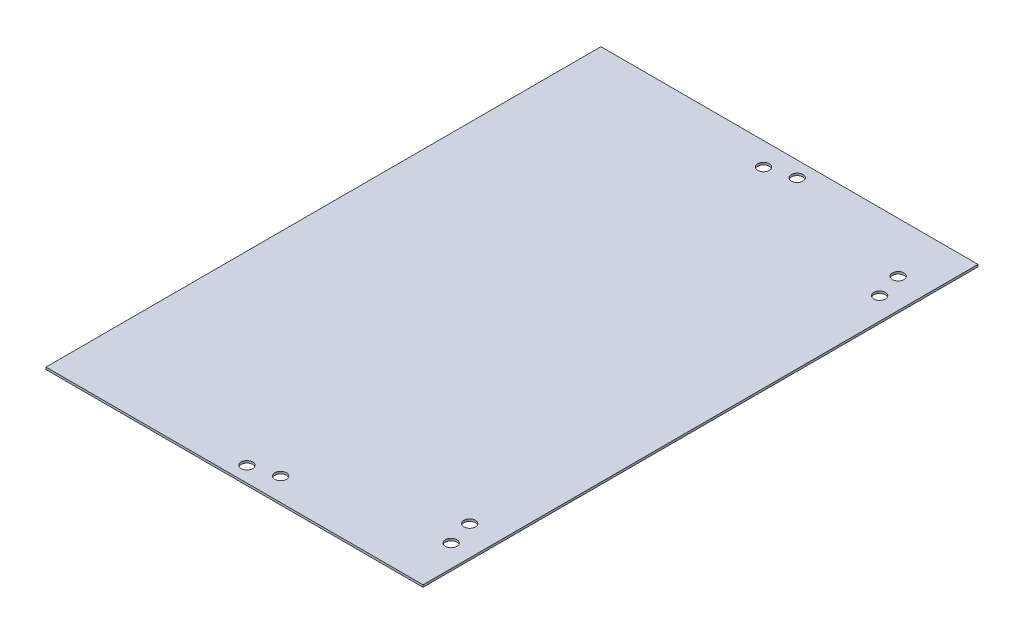
SolidWorks part; units mm, degrees
material "Alumina"
ref_plane "Front Plane" through (0, 0, 0) normal (0, 0, 1) x (1, 0, 0)
ref_plane "Top Plane" through (0, 0, 0) normal (0, 1, 0) x (1, 0, 0)
ref_plane "Right Plane" through (0, 0, 0) normal (1, 0, 0) x (0, 0, -1)
sketch "Sketch3" plane through (0, 0, 0) normal (0, 1, 0) x (1, 0, 0)
  line L1 (-110, 161.9) -> (110, 161.9)
  line L2 (-110, 161.9) -> (-110, -161.9)
  line L3 (-110, -161.9) -> (110, -161.9)
  line L4 (110, 161.9) -> (110, -161.9)
  line L5 (-110, 161.9) -> (110, -161.9) construction
  line L6 (-110, -161.9) -> (110, 161.9) construction
  point P0 (0, 0)
  dimension "D1" = 323.8
  dimension "D2" = 220
extrude "Boss-Extrude1" add sketch "Sketch3" along normal blind 1.2954
sketch "Sketch4" plane through (0, 1.2954, 0) normal (0, 1, 0) x (1, 0, 0)
  circle A0 centre (97.1046, -132.62) radius 3.3782
  circle A1 centre (92.7046, -117.38) radius 3.3782
  circle A2 centre (13.4996, -148.5) radius 3.3782
  circle A3 centre (-1.7404, -152.9) radius 3.3782
  circle A4 centre (97.1046, 117.38) radius 3.3782
  circle A6 centre (92.7046, 132.62) radius 3.3782
  circle A7 centre (13.4996, 152.9) radius 3.3782
  circle A8 centre (-1.7404, 148.5) radius 3.3782
extrude "Cut-Extrude1" cut sketch "Sketch4" against normal up to next
